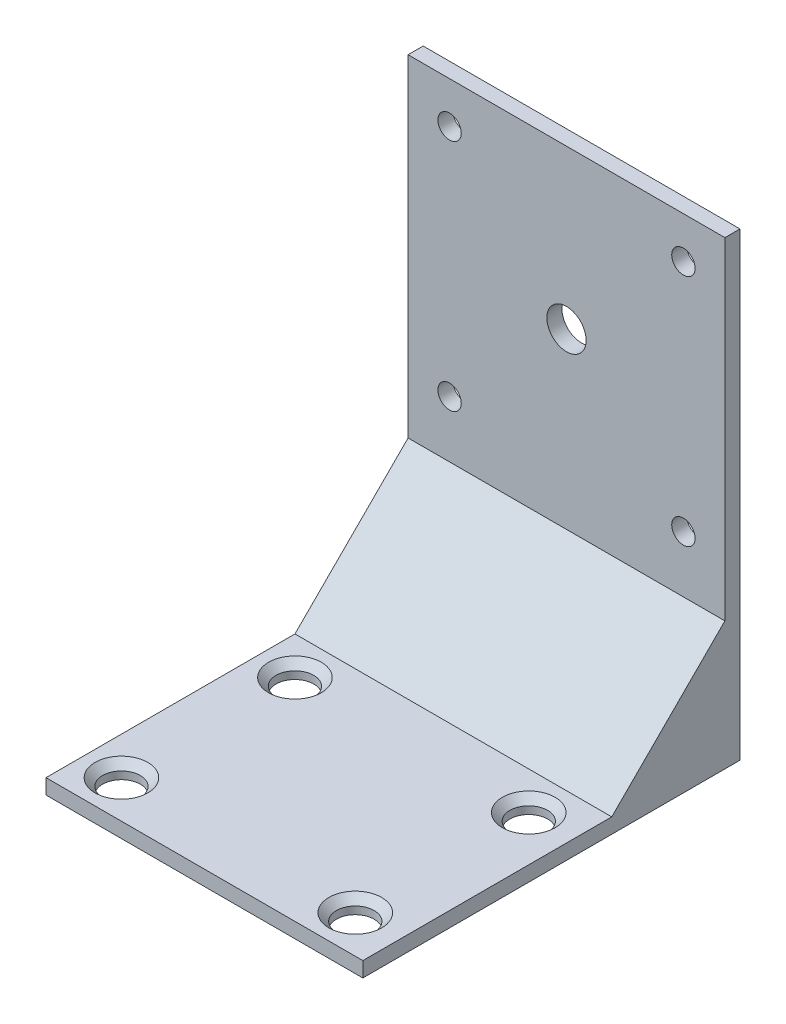
SolidWorks part; units mm, degrees
ref_plane "Plan de face" through (0, 0, 0) normal (0, 0, 1) x (1, 0, 0)
ref_plane "Plan de dessus" through (0, 0, 0) normal (0, 1, 0) x (1, 0, 0)
ref_plane "Plan de droite" through (0, 0, 0) normal (1, 0, 0) x (0, 0, -1)
sketch "Esquisse1" plane through (0, 0, 0) normal (0, 0, 1) x (1, 0, 0)
  line L0 (0, 42) -> (42, 0) construction
  line L1 (0, 0) -> (42, 0)
  line L2 (0, 0) -> (0, 42)
  line L3 (0, 42) -> (42, 42)
  line L4 (42, 0) -> (42, 42)
  line L5 (42, 42) -> (0, 0) construction
  line L7 (0, 0) -> (42, 0)
  line L8 (0, 0) -> (0, -19)
  line L9 (0, -19) -> (42, -19)
  line L10 (42, 0) -> (42, -19)
  circle A0 centre (5.5, 5.5) radius 1.55
  circle A1 centre (36.5, 5.5) radius 1.55
  circle A2 centre (36.5, 36.5) radius 1.55
  circle A3 centre (5.5, 36.5) radius 1.55
  circle A4 centre (21, 21) radius 2.6
  dimension "D5" = 3.1
  dimension "D8" = 5.2
  dimension "D1" = 42
  dimension "D2" = 42
  dimension "D3" = 5.5
  dimension "D4" = 5.5
  dimension "D9" = 40
  dimension "D6" = 2
  dimension "D7" = 2
extrude "Boss.-Extru.1" add sketch "Esquisse1" along normal blind 2 contours L1 L4 L3 L2 A4 A3 A2 A1 A0 | L10 L1 L8 L9 region at (0.594, 21, 0) region at (21, -9.5, 0)
sketch "Esquisse2" plane through (0, 0, 2) normal (0, 0, 1) x (1, 0, 0)
  line L0 (42, -19) -> (42, 42) construction
  line L1 (0, -19) -> (42, -19)
  line L2 (0, -19) -> (0, -17)
  line L3 (0, -17) -> (42, -17)
  line L4 (42, -19) -> (42, -17)
  dimension "D1" = 2
extrude "Boss.-Extru.2" add sketch "Esquisse2" along normal blind 48
sketch "Esquisse3" plane through (42, 0, 0) normal (1, 0, 0) x (0, 0, -1)
  line L0 (-2, -2) -> (-17, -17)
  line L1 (-2, -17) -> (-2, 42) construction
  line L2 (-50, -17) -> (-2, -17) construction
  line L3 (-2, -2) -> (-2, -17)
  line L4 (-2, -17) -> (-17, -17)
  dimension "D1" = 45
  dimension "D2" = 15
extrude "Boss.-Extru.3" add sketch "Esquisse3" against normal up to surface (42 mm away) up to face at (0, 2, 17.3333)
sketch "Esquisse4" plane through (0, -17, 0) normal (0, 1, 0) x (1, 0, 0)
  line L0 (0, -17) -> (42, -17) construction
  line L1 (0, -50) -> (0, -17) construction
  circle A0 centre (5, -22) radius 2.5
  circle A1 centre (36, -22) radius 2.5
  circle A2 centre (36, -45) radius 2.5
  circle A3 centre (5, -45) radius 2.5
  dimension "D1" = 5
  dimension "D2" = 5
  dimension "D3" = 5
  dimension "D4" = 2
  dimension "D5" = 2
extrude "Enlèv. mat.-Extru.4" cut sketch "Esquisse4" against normal up to next
chamfer "Chanfrein1" distance 1 angle 45 4 edges at (36, -17, 47.5) (5, -17, 47.5) (5, -17, 24.5) (36, -17, 24.5)
